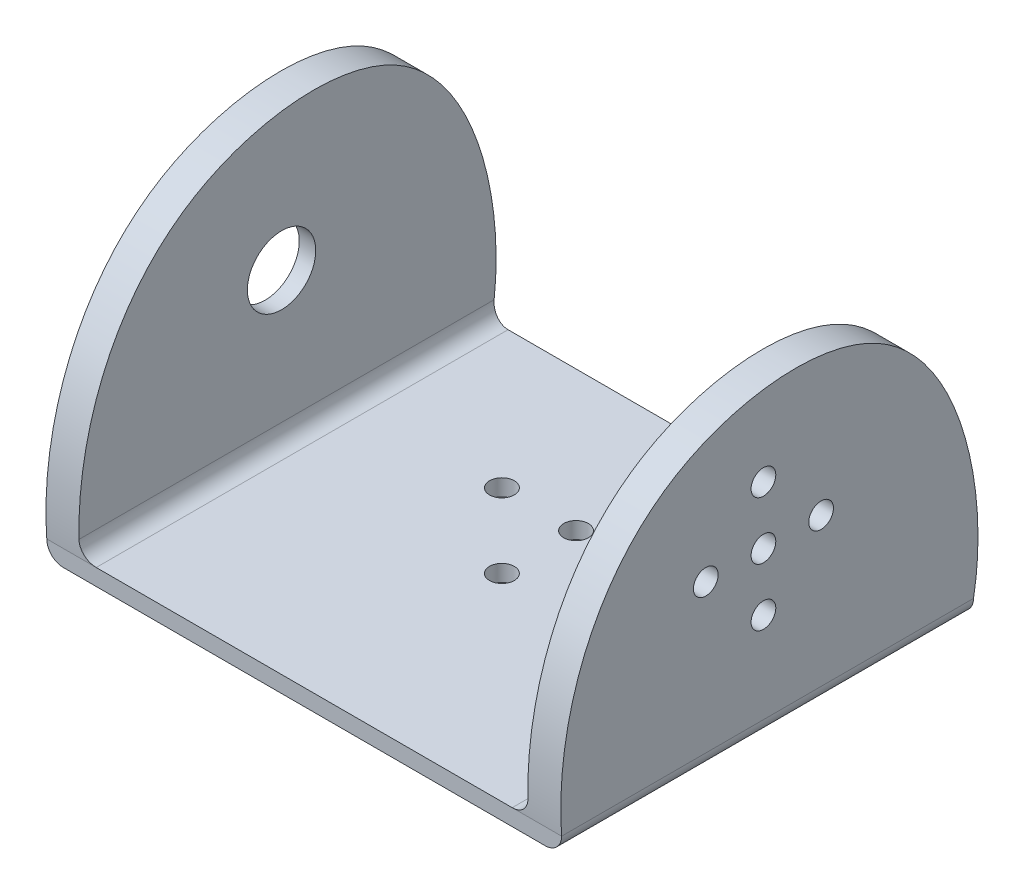
SolidWorks part; units mm, degrees
ref_plane "Front" through (0, 0, 0) normal (0, 0, 1) x (1, 0, 0)
ref_plane "Top" through (0, 0, 0) normal (0, 1, 0) x (1, 0, 0)
ref_plane "Right" through (0, 0, 0) normal (1, 0, 0) x (0, 0, -1)
sketch "Sketch1" plane through (0, 0, 0) normal (0, 1, 0) x (1, 0, 0)
  line L1 (-31.25, -25) -> (31.25, -25)
  line L2 (-31.25, -25) -> (-31.25, 25)
  line L3 (-31.25, 25) -> (31.25, 25)
  line L4 (31.25, -25) -> (31.25, 25)
  line L5 (-31.25, -25) -> (31.25, 25) construction
  line L6 (-31.25, 25) -> (31.25, -25) construction
  point P0 (0, 0)
  dimension "D1" = 62.5
  dimension "D2" = 50
extrude "Boss-Extrude1" add sketch "Sketch1" along normal blind 2
ref_plane "Plane1" through (31.25, 0, 0) normal (1, 0, 0) x (0, 0, -1)
sketch "Sketch2" plane through (31.25, 0, 0) normal (1, 0, 0) x (0, 0, -1)
  line L0 (-25, 2) -> (25, 2) construction
  line L1 (-25, 2) -> (25, 2)
  line L2 (-22.4154, 37) -> (28.2236, 37) construction
  spline S0 degree 3 poles (-25, 2) (-25.8185, 13.3222) (-18.9148, 35.4925) (21.2251, 40.5213) (26.9986, 12.4966) (25, 2) knots 0 0 0 0 0.361133 0.625452 1 1 1 1
  dimension "D1" = 35
extrude "Boss-Extrude2" add sketch "Sketch2" against normal blind 4
mirror "Mirror1" about plane through (0, 0, 0) normal (1, 0, 0) of "Boss-Extrude2"
fillet "Fillet1" radius 2 2 edges
fillet "Fillet2" radius 2 2 edges at (31.25, 0, 0) (-31.25, 0, 0)
sketch "Sketch3" plane through (31.25, 0, 0) normal (1, 0, 0) x (0, 0, -1)
  line L0 (-0.5, 20) -> (-0.5, 50.9601) construction
  line L1 (25, 0) -> (-25, 0) construction
  circle A0 centre (-0.5, 20) radius 1.5
  circle A1 centre (-0.5, 27) radius 1.5
  circle A2 centre (6.5, 20) radius 1.5
  circle A3 centre (-0.5, 13) radius 1.5
  circle A4 centre (-7.5, 20) radius 1.5
  point P0 (-0.5, 20)
  point P7 (0, 0)
  point P18 (-0.5, 13)
  point P19 (-0.5, 20)
  dimension "D1" = 3
  dimension "D2" = 1
  dimension "D4" = 3
  dimension "D3" = 20
  dimension "D5" = 7
  dimension "D6" = 4
extrude "Cut-Extrude1" cut sketch "Sketch3" against normal blind 10
sketch "Sketch4" plane through (0, 2, 0) normal (0, 1, 0) x (1, 0, 0)
  line L0 (0, -126.4282) -> (0, 74.1241) construction
  circle A0 centre (0, 17) radius 1.5
  circle A1 centre (0, -1) radius 1.5
  circle A2 centre (-9, 8) radius 1.5
  circle A3 centre (9, 8) radius 1.5
  circle A4 centre (0, 8) radius 1.5
  point P0 (0, 8)
  point P1 (0, 0)
  dimension "D1" = 3
  dimension "D2" = 3
  dimension "D3" = 3
  dimension "D4" = 3
  dimension "D5" = 3
  dimension "D6" = 9
  dimension "D10" = 8
  dimension "D7" = 9
  dimension "D8" = 9
  dimension "D9" = 9
extrude "Cut-Extrude2" cut sketch "Sketch4" against normal blind 10
sketch "Sketch5" plane through (-31.25, 0, 0) normal (-1, 0, 0) x (0, 0, 1)
  circle A0 centre (0.5, 20) radius 4.15
  point P1 (0.5, 20)
  dimension "D1" = 8.3
extrude "Cut-Extrude3" cut sketch "Sketch5" against normal blind 10
sketch "Sketch6" plane through (-31.25, 0, 0) normal (-1, 0, 0) x (0, 0, 1)
  circle A0 centre (0.5, 20) radius 8
  dimension "D1" = 16
extrude "Cut-Extrude4" cut sketch "Sketch6" against normal blind 2
